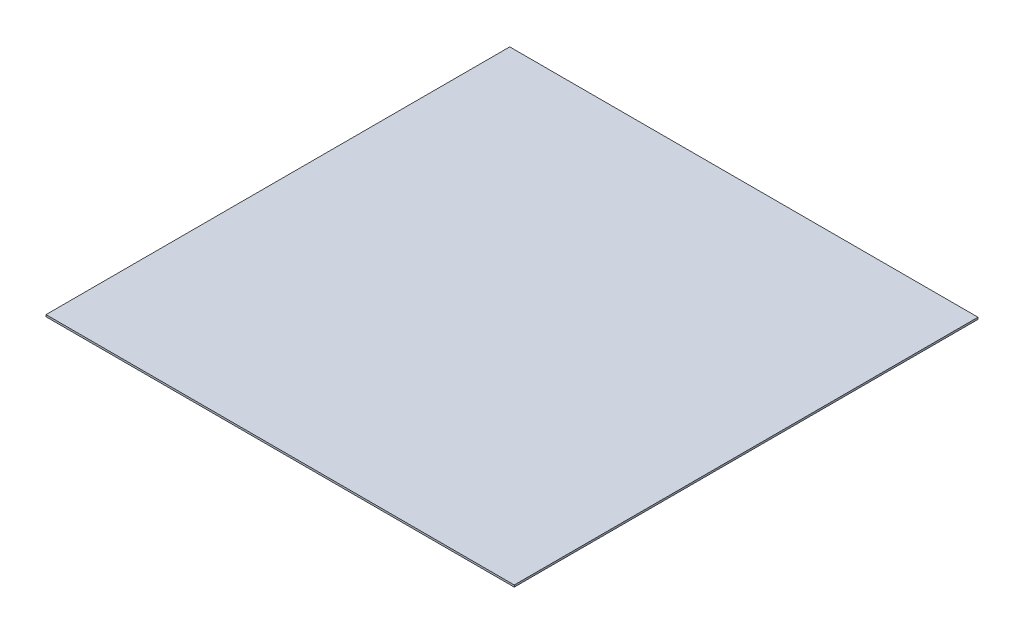
SolidWorks part; units mm, degrees
ref_plane "Front" through (0, 0, 0) normal (0, 0, 1) x (1, 0, 0)
ref_plane "Top" through (0, 0, 0) normal (0, 1, 0) x (1, 0, 0)
ref_plane "Right" through (0, 0, 0) normal (1, 0, 0) x (0, 0, -1)
sketch "Sketch1" plane through (0, 0, 0) normal (0, 1, 0) x (1, 0, 0)
  line L1 (-196.8999, -195) -> (196.8999, -195)
  line L2 (-196.8999, -195) -> (-196.8999, 195)
  line L3 (-196.8999, 195) -> (196.8999, 195)
  line L4 (196.8999, -195) -> (196.8999, 195)
  line L5 (-196.8999, -195) -> (196.8999, 195) construction
  line L6 (-196.8999, 195) -> (196.8999, -195) construction
  point P0 (0, 0)
  dimension "D1" = 393.7998
  dimension "D2" = 390
base flange "Base-Flange1" sketch "Sketch1" thickness 1.5875 reverse thickness direction no parameters "D1"=0.381
sketch "Bend-Lines3" [suppressed] plane through (0, 0, 0) normal (0, 1, 0) x (1, 0, 0)
sketch "Bounding-Box3" [suppressed] plane through (0, 0, 0) normal (0, 1, 0) x (1, 0, 0)
sheet metal parameters "Sheet-Metal5" thickness 1.5875 parameters "D1"=0.381
flat pattern "Flat-Pattern5" [suppressed]
sketch "Bend-Lines4" plane through (0, 0, 0) normal (0, 1, 0) x (1, 0, 0)
sketch3d "Bounding-Box4" [suppressed]
  line L0 (196.8999, 195, 0) -> (-196.8999, 195, 0) construction
  line L1 (196.8999, -195, 0) -> (-196.8999, -195, 0) construction
  line L2 (196.8999, 195, 0) -> (196.8999, -195, 0) construction
  line L3 (-196.8999, 195, 0) -> (-196.8999, -195, 0) construction
